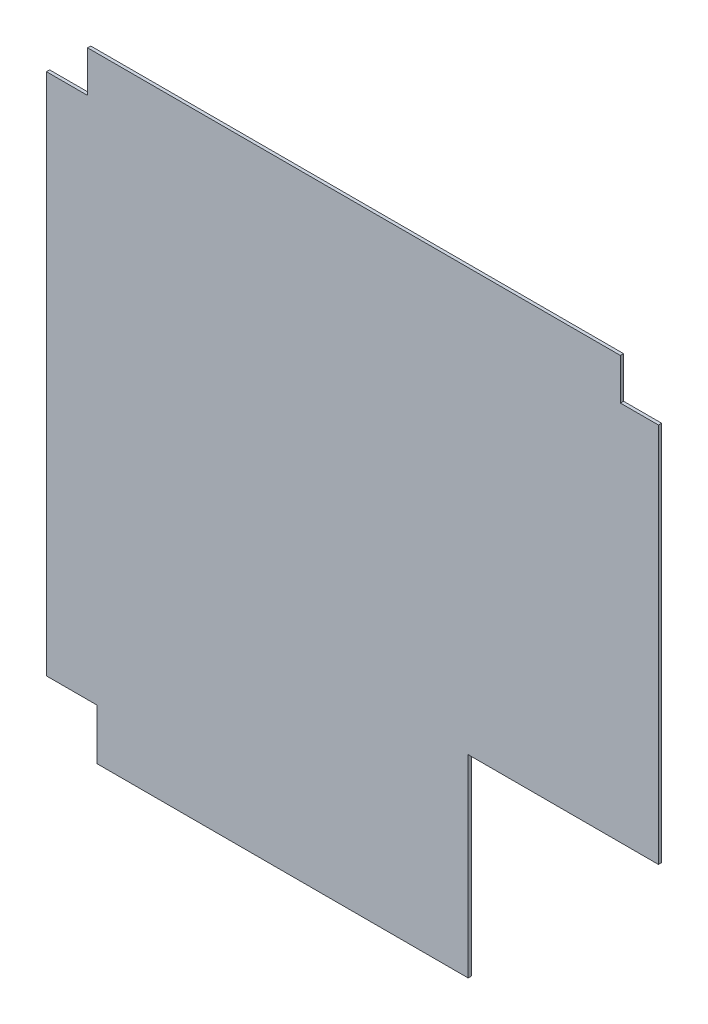
SolidWorks part; units mm, degrees
ref_plane "Front Plane" through (0, 0, 0) normal (0, 0, 1) x (1, 0, 0)
ref_plane "Top Plane" through (0, 0, 0) normal (0, 1, 0) x (1, 0, 0)
ref_plane "Right Plane" through (0, 0, 0) normal (1, 0, 0) x (0, 0, -1)
sketch "Sketch1" plane through (0, 0, 0) normal (0, 0, 1) x (1, 0, 0)
  line L1 (-371.475, -307.975) -> (371.475, -307.975)
  line L2 (-371.475, -307.975) -> (-371.475, 307.975)
  line L3 (-371.475, 307.975) -> (371.475, 307.975)
  line L4 (371.475, -307.975) -> (371.475, 307.975)
  line L5 (-371.475, -307.975) -> (371.475, 307.975) construction
  line L6 (-371.475, 307.975) -> (371.475, -307.975) construction
  point P0 (0, 0)
  dimension "D1" = 742.95
  dimension "D2" = 615.95
extrude "Boss-Extrude1" add sketch "Sketch1" along normal blind 3.175
sketch "Sketch2" plane through (0, 0, 3.175) normal (0, 0, 1) x (1, 0, 0)
  line L0 (371.475, 307.975) -> (-371.475, 307.975) construction
  line L1 (-371.475, 307.975) -> (-330.2, 307.975)
  line L2 (-371.475, 307.975) -> (-371.475, 266.7)
  line L3 (-371.475, 266.7) -> (-330.2, 266.7)
  line L4 (-330.2, 307.975) -> (-330.2, 266.7)
  line L5 (-371.475, 307.975) -> (-371.475, -307.975) construction
  line L6 (371.475, -307.975) -> (371.475, 307.975) construction
  line L7 (-371.475, -307.975) -> (-320.675, -307.975)
  line L8 (-371.475, -307.975) -> (-371.475, -257.175)
  line L9 (-371.475, -257.175) -> (-320.675, -257.175)
  line L10 (-320.675, -307.975) -> (-320.675, -257.175)
  line L11 (203.2, 307.975) -> (241.3, 307.975)
  line L12 (203.2, 307.975) -> (203.2, 266.7)
  line L13 (203.2, 266.7) -> (241.3, 266.7)
  line L14 (241.3, 307.975) -> (241.3, 266.7)
  line L15 (-371.475, -307.975) -> (371.475, -307.975) construction
  line L16 (50.8, -307.975) -> (241.3, -307.975)
  line L17 (50.8, -307.975) -> (50.8, -114.3)
  line L18 (50.8, -114.3) -> (241.3, -114.3)
  line L19 (241.3, -307.975) -> (241.3, -114.3)
  point P26 (-330.2, -255.2379)
  dimension "D1" = 41.275
  dimension "D2" = 41.275
  dimension "D3" = 130.175
  dimension "D4" = 38.1
  dimension "D5" = 152.4
  dimension "D6" = 193.675
  dimension "D7" = 50.8
  dimension "D8" = 50.8
extrude "Cut-Extrude1" cut sketch "Sketch2" against normal through all
sketch "Sketch3" plane through (0, 0, 3.175) normal (0, 0, 1) x (1, 0, 0)
  line L1 (371.475, 307.975) -> (241.3, 307.975)
  line L2 (371.475, 307.975) -> (371.475, -307.975)
  line L3 (371.475, -307.975) -> (241.3, -307.975)
  line L4 (241.3, 307.975) -> (241.3, -307.975)
extrude "Cut-Extrude2" cut sketch "Sketch3" against normal through all
